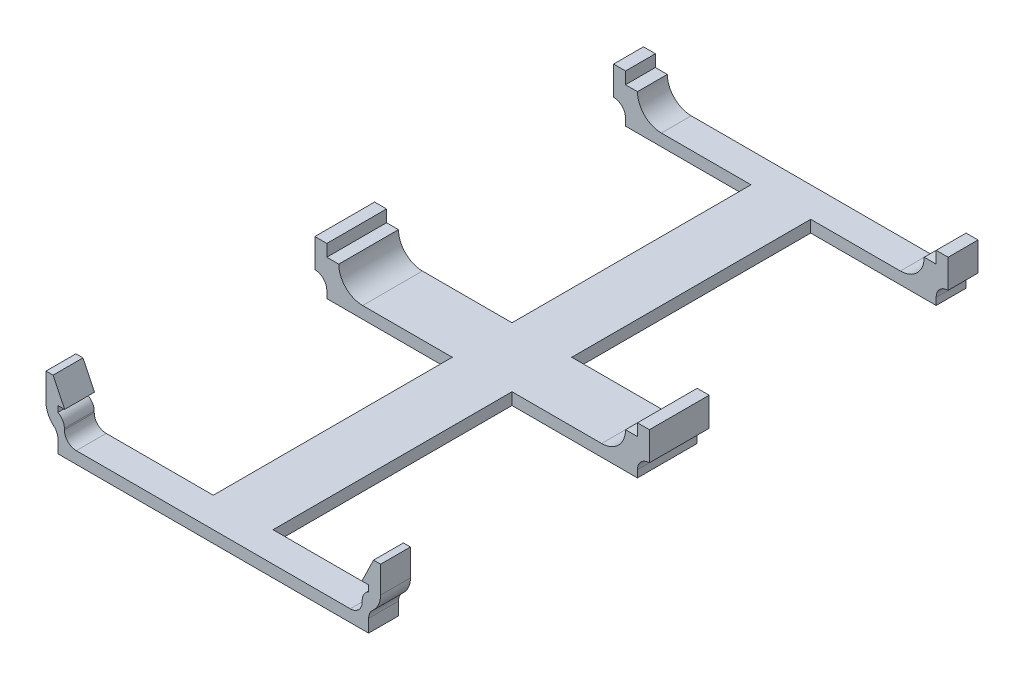
SolidWorks part; units mm, degrees
ref_plane "Front Plane" through (0, 0, 0) normal (0, 0, 1) x (1, 0, 0)
ref_plane "Top Plane" through (0, 0, 0) normal (0, 1, 0) x (1, 0, 0)
ref_plane "Right Plane" through (0, 0, 0) normal (1, 0, 0) x (0, 0, -1)
sketch "Sketch1" plane through (0, 0, 0) normal (0, 0, 1) x (1, 0, 0)
  line L0 (0, 0) -> (13.1581, 0)
  line L8 (13.1581, 1.27) -> (-2.0819, 1.27)
  line L9 (-2.0819, 1.27) -> (-2.0819, 3.81)
  line L10 (-2.0819, 3.81) -> (-3.3519, 3.81)
  line L11 (-3.3519, 3.81) -> (-3.3519, 5.08)
  line L12 (-3.3519, 5.08) -> (-4.6219, 5.08)
  line L13 (-4.6219, 5.08) -> (-4.6219, 2.032)
  line L14 (-4.6219, 2.032) -> (-3.3519, 2.032)
  line L15 (-3.3519, 2.032) -> (-3.3519, 0)
  line L16 (-3.3519, 0) -> (0, 0)
  line L17 (13.1581, 0) -> (13.1581, 16.1586) construction
  line L18 (13.1581, 1.27) -> (13.1581, 0)
  dimension "D1" = 16.51
  dimension "D2" = 1.27
  dimension "D3" = 1.27
  dimension "D4" = 1.778
  dimension "D6" = 1.27
  dimension "D7" = 2.54
  dimension "D8" = 1.27
extrude "Boss-Extrude1" add sketch "Sketch1" against normal blind 63.5 contours L8 L9 L10 L11 L12 L13 L14 L15 L16 L0 L18
mirror "Mirror1" about plane through (13.1581, 1.27, -63.5) normal (-1, 0, 0) of "Boss-Extrude1"
sketch "Sketch2" plane through (0, 5.08, 0) normal (0, 1, 0) x (1, 0, 0)
  line L0 (-4.6219, 63.5) -> (-4.6219, 0) construction
  line L1 (-4.6219, 3.175) -> (9.9831, 3.175)
  line L2 (-4.6219, 3.175) -> (-4.6219, 28.575)
  line L3 (-4.6219, 28.575) -> (9.9831, 28.575)
  line L4 (30.9381, 3.175) -> (30.9381, 28.575)
  line L5 (30.9381, 63.5) -> (30.9381, 0) construction
  line L6 (9.9831, 60.325) -> (-4.6219, 60.325)
  line L7 (30.9381, 34.925) -> (16.3331, 34.925)
  line L8 (30.9381, 34.925) -> (30.9381, 60.325)
  line L9 (30.9381, 60.325) -> (16.3331, 60.325)
  line L10 (-4.6219, 34.925) -> (-4.6219, 60.325)
  line L12 (9.9831, 60.325) -> (9.9831, 34.925)
  line L14 (16.3331, 60.325) -> (16.3331, 34.925)
  line L16 (16.3331, 28.575) -> (16.3331, 3.175)
  line L18 (9.9831, 28.575) -> (9.9831, 3.175)
  line L19 (9.9831, 34.925) -> (-4.6219, 34.925)
  line L20 (16.3331, 28.575) -> (30.9381, 28.575)
  line L21 (16.3331, 3.175) -> (30.9381, 3.175)
  line L22 (13.1581, 63.5) -> (13.1581, 0) construction
  line L23 (28.3981, 63.5) -> (-2.0819, 63.5) construction
  line L24 (28.3981, 0) -> (-2.0819, 0) construction
  line L25 (-4.6219, 31.75) -> (30.9381, 31.75) construction
  dimension "D1" = 6.35
  dimension "D2" = 6.35
  dimension "D3" = 3.175
  dimension "D4" = 6.35
  dimension "D5" = 3.175
  dimension "D6" = 3.175
  dimension "D7" = 3.175
  dimension "D8" = 3.175
extrude "Cut-Extrude1" cut sketch "Sketch2" against normal up to surface (5.08 mm away) up to face at (13.1581, 0, -31.75)
sketch "Sketch3" plane through (0, 0, 0) normal (0, 0, 1) x (1, 0, 0)
  line L0 (-4.6219, 4.445) -> (-2.6377, 4.445)
  line L1 (-4.6219, 5.08) -> (-4.6219, 2.032) construction
  line L3 (-4.6219, 6.985) -> (-4.6219, 4.445)
  line L4 (-4.6219, 6.985) -> (-3.8704, 6.985)
  line L5 (-3.3519, 5.08) -> (-4.6219, 5.08) construction
  line L6 (-3.8704, 6.985) -> (-2.6377, 4.445)
  dimension "D1" = 0.635
  dimension "D2" = 2.54
extrude "Boss-Extrude2" add sketch "Sketch3" against normal up to surface (3.175 mm away) up to face at (-0.6849, 2.4384, -3.175)
ref_plane "Plane1" through (13.1581, 0, 0) normal (-1, 0, 0) x (0, 0, 1)
mirror "Mirror2" about plane through (13.1581, 0, 0) normal (-1, 0, 0) of "Boss-Extrude2"
sketch "Sketch4" plane through (0, 0, 0) normal (0, 0, 1) x (1, 0, 0)
  line L0 (28.3981, 1.27) -> (-2.0819, 1.27) construction
  line L1 (-2.0819, 3.81) -> (-2.6709, 3.81)
  line L2 (-2.0819, 3.81) -> (-2.0819, 1.27)
  line L3 (-2.0819, 1.27) -> (-2.6709, 1.27)
  line L4 (-2.6709, 3.81) -> (-2.6709, 1.27)
extrude "Cut-Extrude2" cut sketch "Sketch4" against normal up to next
mirror "Mirror3" about plane through (13.1581, 0, 0) normal (-1, 0, 0) of "Cut-Extrude2"
fillet "Fillet1" radius 2.38 6 edges at (-3.9869, 2.032, 0) (30.3031, 2.032, -3.175) (-3.9869, 2.032, -3.175) (30.3031, 2.032, 0) (30.9381, 2.032, -1.5875) (-4.6219, 2.032, -1.5875)
fillet "Fillet2" radius 1.27 4 edges at (-3.3519, 2.032, -1.5875) (29.6681, 2.032, -1.5875) (28.9871, 3.81, -1.5875) (-2.6709, 3.81, -1.5875)
fillet "Fillet3" radius 2.54 4 edges at (28.3981, 1.27, -31.75) (28.3981, 1.27, -61.9125) (-2.0819, 1.27, -61.9125) (-2.0819, 1.27, -31.75)
fillet "Fillet5" radius 1.27 4 edges at (29.6681, 2.032, -61.9125) (29.6681, 2.032, -31.75) (-3.3519, 2.032, -61.9125) (-3.3519, 2.032, -31.75)
fillet "Fillet6" radius 1.27 2 edges at (28.9871, 1.27, -1.5875) (-2.6709, 1.27, -1.5875)
equation "\"D3@Sketch2\"=\"D2@Sketch2\"/2"
equation "\"D4@Sketch2\"=\"D2@Sketch2\""
equation "\"D5@Sketch2\"=\"D3@Sketch2\""
equation "\"D8@Sketch2\"=\"D1@Sketch2\"/2"
